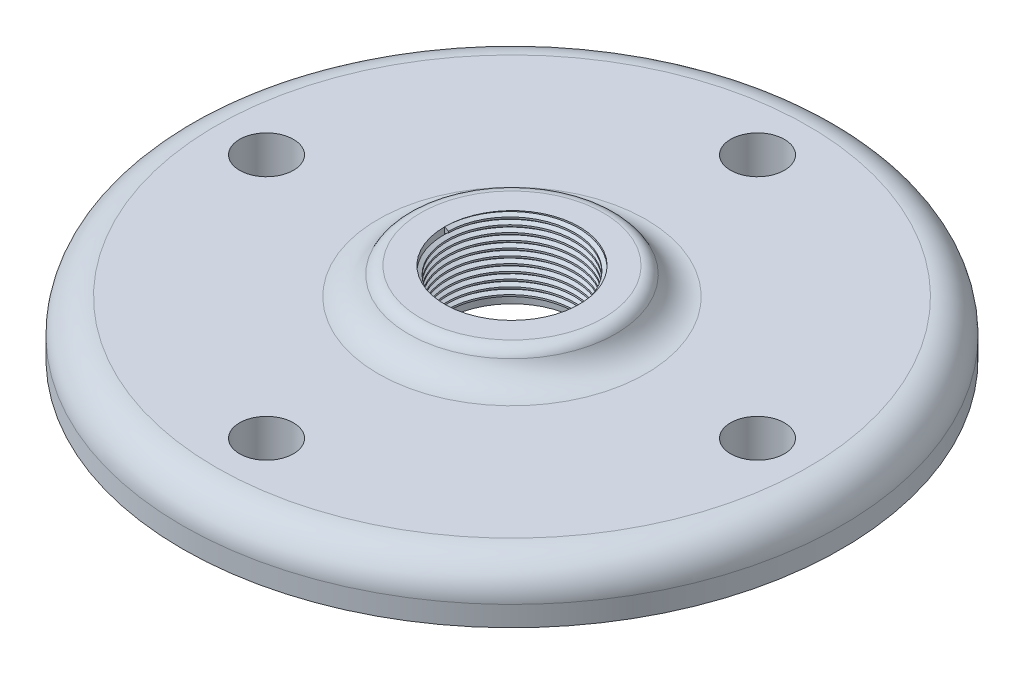
SolidWorks part; units mm, degrees
material "Malleable Cast Iron"
ref_plane "Front Plane" through (0, 0, 0) normal (0, 0, 1) x (1, 0, 0)
ref_plane "Top Plane" through (0, 0, 0) normal (0, 1, 0) x (1, 0, 0)
ref_plane "Right Plane" through (0, 0, 0) normal (1, 0, 0) x (0, 0, -1)
sketch "Sketch1" plane through (0, 0, 0) normal (0, 1, 0) x (1, 0, 0)
  circle A0 centre (0, 0) radius 49
  circle A1 centre (0, 0) radius 36.5
  circle A2 centre (0, 36.5) radius 4
  circle A3 centre (36.5, 0) radius 4
  circle A4 centre (0, -36.5) radius 4
  circle A5 centre (-36.5, 0) radius 4
  circle A6 centre (0, 0) radius 10
  circle A7 centre (0, 0) radius 15
  point P15 (0, 0)
  dimension "D2" = 8
  dimension "D3" = 73
  dimension "D4" = 98
  dimension "D5" = 20
  dimension "D6" = 30
  dimension "D1" = 4
extrude "Boss-Extrude2" add sketch "Sketch1" along normal blind 8 contours A0 A5 A1 A2 A3 A4 | A5 A1 A4 A3 A2 A7 region at (-47.6141, 0, 0) region at (31.4738, 0, 0)
extrude "Boss-Extrude3" add sketch "Sketch1<4>" along normal blind 12 contours A7 A6 region at (-14.5757, 0, 0)
sketch "Sketch1<4>" plane through (0, 0, 0) normal (0, 1, 0) x (1, 0, 0) same geometry as "Sketch1"
fillet "Fillet2" radius 5 2 edges at (0, 8, 15) (0, 8, 49)
fillet "Fillet3" radius 2 1 edges at (0, 12, 15)
thread "Thread1" pitch 1 method extrude profile "Thread Profile3" start angle 0, offset 0, length 11, pitch 1, diameter 20
ref_plane "Plane3" through (-10, 12, 0) normal (0, 0, 1) x (-1, 0, 0)
sketch "Thread Profile3" plane through (-10, 12, 0) normal (0, 0, 1) x (-1, 0, 0)
  line L0 (0, 0) -> (0, 1) construction
  line L11 (0, 0) -> (0, 0.875)
  line L12 (0, 0.875) -> (-0.5413, 0.5625)
  line L13 (-0.5413, 0.5625) -> (-0.5413, 0.3125)
  line L15 (-0.5413, 0.3125) -> (0, 0)
  line L17 (-0.5413, 0.4375) -> (0, 0.4375) construction
  point P2 (0, 0)
  dimension "Pitch" = 1
  dimension "Profile_Angle" = 60
  dimension "Profile_Land" = 0.25
  dimension "Profile_Height" = 0.5413
